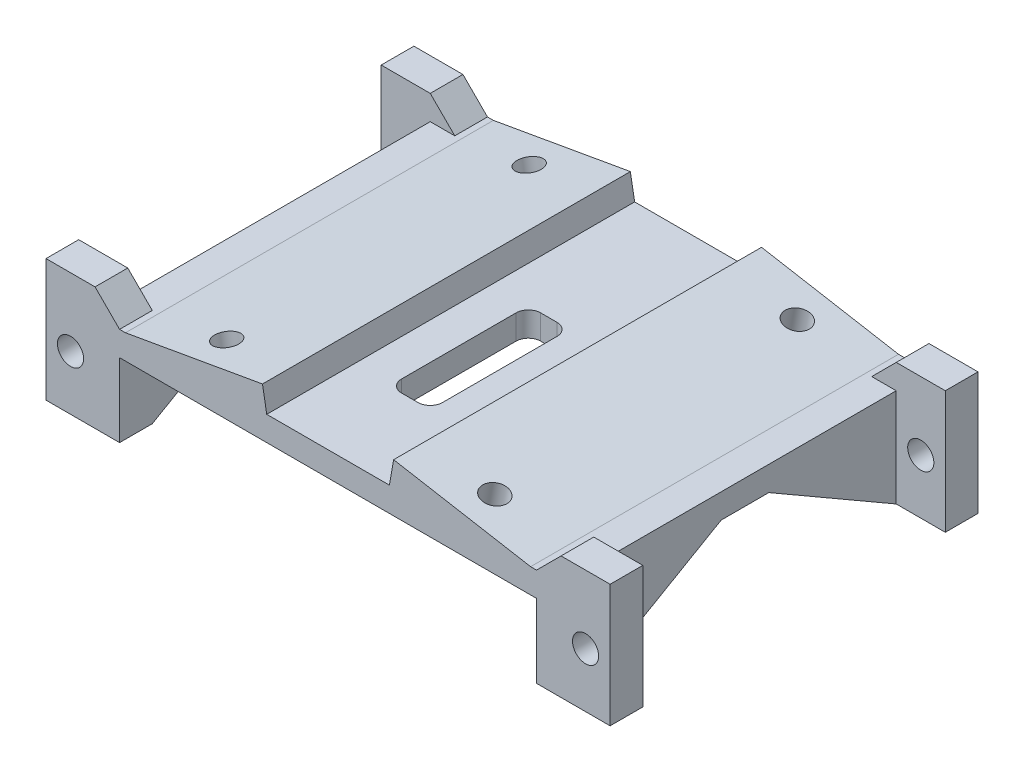
SolidWorks part; units mm, degrees
ref_plane "前视基准面" through (0, 0, 0) normal (0, 0, 1) x (1, 0, 0)
ref_plane "上视基准面" through (0, 0, 0) normal (0, 1, 0) x (1, 0, 0)
ref_plane "右视基准面" through (0, 0, 0) normal (1, 0, 0) x (0, 0, -1)
sketch "草图1" plane through (0, 0, 0) normal (0, 1, 0) x (1, 0, 0)
  line L1 (0, 0) -> (57, 0)
  line L2 (0, 0) -> (0, 45)
  line L3 (0, 45) -> (57, 45)
  line L4 (57, 0) -> (57, 45)
  dimension "D1" = 45
  dimension "D2" = 57
extrude "凸台-拉伸1" add sketch "草图1" along normal blind 3
sketch "草图2" plane through (0, 0, 0) normal (-1, 0, 0) x (0, 0, 1)
  line L0 (0, 6) -> (-4, 6)
  line L1 (-4, 6) -> (-4, -9)
  line L2 (-4, -9) -> (0, -9)
  line L3 (0, -9) -> (0, 6)
  line L4 (-45, 3) -> (0, 3) construction
  line L5 (-45, 0) -> (0, 0) construction
  line L8 (0, 3) -> (0, 0) construction
  dimension "D1" = 3
  dimension "D2" = 9
  dimension "D3" = 4
extrude "凸台-拉伸2" add sketch "草图2" along normal blind 6
sketch "草图3" plane through (57, 0, 0) normal (1, 0, 0) x (0, 0, -1)
  line L0 (0, 6) -> (0, -9)
  line L1 (0, -9) -> (4, -9)
  line L2 (4, -9) -> (4, 6)
  line L3 (4, 6) -> (0, 6)
extrude "凸台-拉伸3" add sketch "草图3" along normal blind 6
sketch "草图4" plane through (57, 0, 0) normal (-1, 0, 0) x (0, 0, 1)
  line L0 (-4, -9) -> (-19.5885, 0)
  line L1 (-4, 0) -> (-45, 0) construction
  line L2 (-19.5885, 0) -> (0, 0)
  line L3 (0, 0) -> (0, -9)
  line L4 (0, -9) -> (-4, -9)
  dimension "D1" = 30
extrude "凸台-拉伸4" add sketch "草图4" along normal blind 3
sketch "草图5" plane through (0, 0, 0) normal (1, 0, 0) x (0, 0, -1)
  line L0 (0, 0.3045) -> (0, -9)
  line L1 (0, -9) -> (4, -9)
  line L2 (4, -9) -> (19.5885, 0)
  line L3 (45, 0) -> (4, 0) construction
  line L4 (19.5885, 0) -> (0, 0)
  line M3 (4, -9) -> (4, 0)
  line M4 (4, 0) -> (0, 0)
  line M5 (0, 0) -> (0, -9)
  line M6 (0, -9) -> (4, -9)
  dimension "D1" = 30
extrude "凸台-拉伸5" add sketch "草图5" along normal blind 3 contours L2 L4 M3 | M6 M3 M4 M5 region at (0, -4.5, -2) region at (0, -3, -9.1962)
chamfer "倒角1" distance 3 angle 45 2 edges at (0, 3, -2) (57, 3, -2)
sketch "草图6" plane through (0, 0, -4) normal (0, 0, -1) x (-1, 0, 0)
  line L0 (-60, -2.3233) -> (3, -2.3233) construction
  line L1 (-63, -9) -> (-63, 6) construction
  line L2 (6, 6) -> (6, -9) construction
  circle A0 centre (3, -2.3233) radius 1.6
  circle A1 centre (-60, -2.3233) radius 1.6
  dimension "D1" = 3
  dimension "D2" = 3
extrude "切除-拉伸1" cut sketch "草图6" against normal blind 4
sketch "草图7" plane through (0, 3, 0) normal (0, 1, 0) x (1, 0, 0)
  line L0 (28, 49.7957) -> (28, -5.721) construction
  line L1 (8, 41) -> (8, 4)
  line L2 (3, 0) -> (54, 0) construction
  line L3 (0, 45) -> (0, 4) construction
  line L4 (48, 41) -> (48, 4)
  circle A0 centre (8, 41) radius 1.6
  circle A1 centre (8, 4) radius 1.6
  circle A2 centre (48, 4) radius 1.6
  circle A3 centre (48, 41) radius 1.6
  dimension "D1" = 37
  dimension "D2" = 4
  dimension "D3" = 8
extrude "切除-拉伸2" [suppressed] cut sketch "草图7" against normal blind 3 contours A3 | A2 | A0 | A1
sketch "草图8" plane through (0, 0, 0) normal (0, -1, 0) x (1, 0, 0)
  line L0 (24, -45) -> (32, -45)
  line L1 (57, -45) -> (0, -45) construction
  line L2 (32, -45) -> (32, -42)
  line L3 (32, -42) -> (24, -42)
  line L4 (24, -42) -> (24, -45)
  line L5 (28, 5.34) -> (28, -50.6665) construction
  line L6 (0, -45) -> (0, -19.5885) construction
  point P10 (32, -43.5)
  dimension "D1" = 28
  dimension "D2" = 3
  dimension "D3" = 8
  dimension "D4" = 4
extrude "凸台-拉伸6" add sketch "草图8" along normal blind 9
sketch "草图9" plane through (32, 0, 0) normal (1, 0, 0) x (0, 0, -1)
  line L0 (45, 0) -> (29.1467, 0)
  line L1 (29.1467, 0) -> (42, -9)
  line L2 (42, -9) -> (45, -9)
  line L3 (45, -9) -> (45, 0)
  dimension "D1" = 35
extrude "凸台-拉伸7" add sketch "草图9" along normal blind 3
sketch "草图10" plane through (24, 0, 0) normal (-1, 0, 0) x (0, 0, 1)
  line L0 (-45, 0) -> (-45, -9)
  line L1 (-45, -9) -> (-42, -9)
  line L2 (-42, -9) -> (-29.1467, 0)
  line L3 (-29.1467, 0) -> (-45, 0)
extrude "凸台-拉伸8" add sketch "草图10" along normal blind 3
sketch "草图11" plane through (0, 0, -42) normal (0, 0, 1) x (1, 0, 0)
  line L0 (24, -9) -> (24, 0) construction
  line L1 (32, -9) -> (24, -9) construction
  circle A0 centre (28, -4.5) radius 1.6
  dimension "D1" = 4
  dimension "D2" = 4.5
extrude "切除-拉伸3" cut sketch "草图11" against normal blind 3
sketch "草图12" plane through (0, 3, 0) normal (0, 1, 0) x (1, 0, 0)
  line L0 (28, 49.4691) -> (28, -3.816) construction
  line L1 (25.5, 27.5) -> (25.5, 10.5)
  line L2 (25.5, 10.5) -> (30.5, 10.5)
  line L3 (30.5, 10.5) -> (30.5, 27.5)
  line L4 (30.5, 27.5) -> (25.5, 27.5)
  line L5 (0, 45) -> (0, 4) construction
  line L6 (-5.009, 22.5) -> (59.3487, 22.5) construction
  line L7 (3, 0) -> (54, 0) construction
  dimension "D1" = 28
  dimension "D2" = 2.5
  dimension "D3" = 2.5
  dimension "D4" = 22.5
  dimension "D5" = 5
  dimension "D6" = 12
extrude "切除-拉伸4" cut sketch "草图12" against normal blind 3
fillet "圆角1" radius 1.5 4 edges at (30.5, 1.5, -10.5) (25.5, 1.5, -10.5) (25.5, 1.5, -27.5) (30.5, 1.5, -27.5)
ref_plane "基准面1" through (28.5, 0, 0) normal (1, 0, 0) x (0, 0, -1)
sketch "草图13" plane through (0, 3, 0) normal (0, 1, 0) x (1, 0, 0)
  line L0 (36, 45) -> (36, 0) construction
  line L1 (57, 45) -> (0, 45) construction
  line L2 (3, 0) -> (54, 0) construction
  line L3 (57, 4) -> (57, 45) construction
  dimension "D1" = 21
ref_plane "基准面2" through (34.4014, -6.0659, 0) normal (0.9848, -0.1736, 0) x (0, 0, 1)
sketch "草图14" plane through (34.4014, -6.0659, 0) normal (0.9848, -0.1736, 0) x (0, 0, 1)
  line L0 (-45, -9.2058) -> (0, -9.2058) construction
  line L1 (-45, -9.2058) -> (0, -9.2058) construction
  line L3 (-45, -9.2058) -> (0, -9.2058) construction
  line L4 (-45, -9.2058) -> (-45, -12.2058) construction
  line L5 (-45, -12.2058) -> (0, -12.2058) construction
  line L6 (0, -9.2058) -> (0, -12.2058) construction
  dimension "D1" = 3
ref_plane "基准面3" through (2.1195, 12.0203, 0) normal (0.1736, 0.9848, 0) x (0, 0, 1)
sketch "草图15" plane through (2.1195, 12.0203, 0) normal (0.1736, 0.9848, 0) x (0, 0, 1)
  line L1 (-45, 34.9321) -> (0, 34.9321)
  line L2 (-45, 34.9321) -> (-45, 52.6587)
  line L3 (-45, 52.6587) -> (0, 52.6587)
  line L4 (0, 34.9321) -> (0, 52.6587)
extrude "凸台-拉伸9" add sketch "草图15" against normal up to body separate body
sketch "草图16" plane through (2.1195, 12.0203, 0) normal (0.1736, 0.9848, 0) x (0.9848, -0.1736, 0)
  line L0 (43.4391, 45) -> (43.4391, 0) construction
  line L1 (51.946, 45) -> (34.9321, 45) construction
  line L2 (34.9321, 0) -> (51.946, 0) construction
  line L3 (51.946, 22.5) -> (43.4391, 22.5) construction
  line L4 (51.946, 45) -> (51.946, 0) construction
  circle A0 centre (43.4391, 41) radius 1.5
  circle A1 centre (43.4391, 4) radius 1.5
  dimension "D1" = 3
  dimension "D2" = 18.5
extrude "切除-拉伸5" cut sketch "草图16" against normal through all
mirror "镜向1" about plane through (28.5, 0, 0) normal (1, 0, 0) of "切除-拉伸5", "凸台-拉伸9"
ref_plane "基准面4" through (0, 0, -22.5) normal (0, 0, 1) x (1, 0, 0)
mirror "镜向2" about plane through (0, 0, -22.5) normal (0, 0, 1) of "倒角1", "凸台-拉伸5", "凸台-拉伸4", "凸台-拉伸3", "凸台-拉伸2", "切除-拉伸1"
